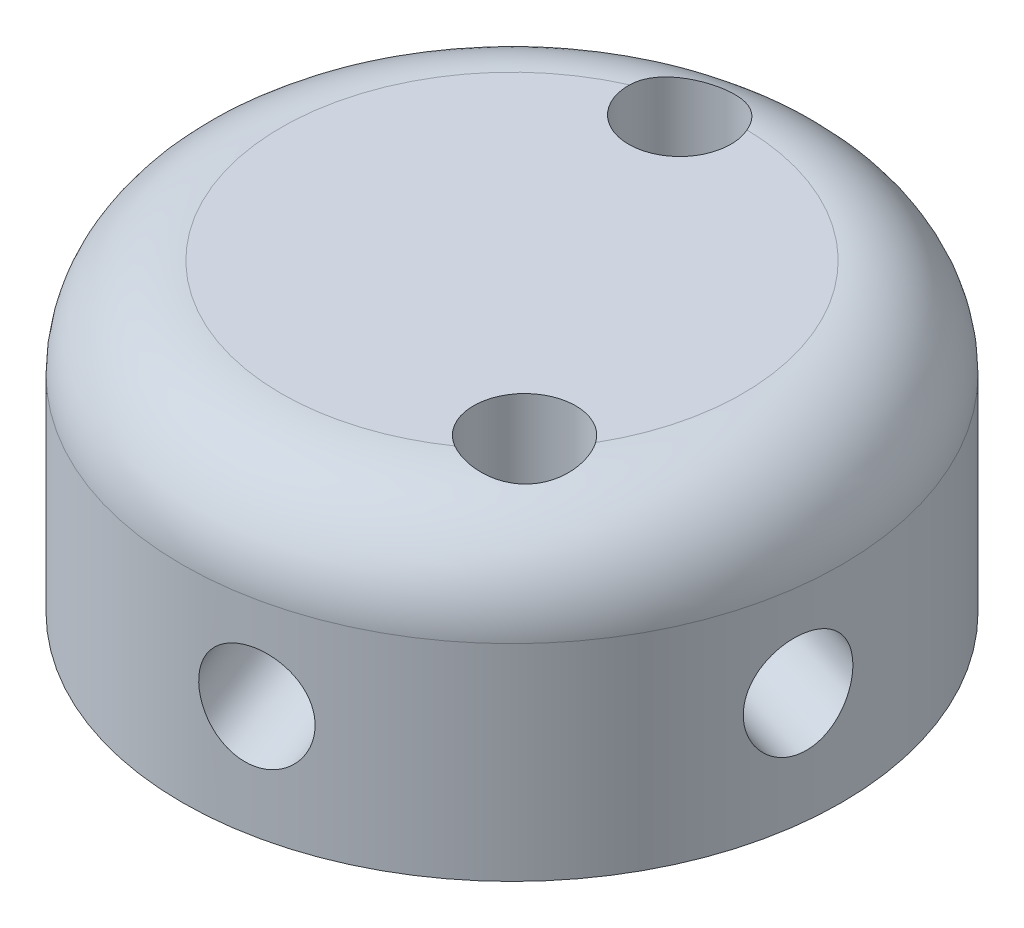
SolidWorks part; units mm, degrees
ref_plane "Front Plane" through (0, 0, 0) normal (0, 0, 1) x (1, 0, 0)
ref_plane "Top Plane" through (0, 0, 0) normal (0, 1, 0) x (1, 0, 0)
ref_plane "Right Plane" through (0, 0, 0) normal (1, 0, 0) x (0, 0, -1)
sketch "Sketch1" plane through (0, 0, 0) normal (0, 1, 0) x (1, 0, 0)
  circle A0 centre (0, 0) radius 10
  dimension "D1" = 20
extrude "Boss-Extrude1" add sketch "Sketch1" along normal blind 3 and the other way blind 10
ref_axis "5hubaxis" through (0, 5.5, 0) along (0, -1, 0)
ref_plane "holeplane" through (-3.3529, -1.0931, 1.8877) normal (0.8382, 0.2733, -0.4719) x (-0.4487, -0.1463, -0.8816)
sketch "Sketch4" plane through (-3.3529, -1.0931, 1.8877) normal (0.8382, 0.2733, -0.4719) x (-0.4487, -0.1463, -0.8816)
  circle A0 centre (0, 0) radius 1.5 construction
  circle A1 centre (0, 0) radius 1.5
extrude "hole" cut sketch "Sketch4" against normal through all
pattern_circular "holecir" count 5 over 360 about axis through (0, 5.5, 0) along (0, -1, 0) of "hole"
sketch "Sketch5" plane through (0, -10, 0) normal (0, -1, 0) x (1, 0, 0)
  line L0 (-10, 0) -> (10, 0) construction
  circle A0 centre (0, 0) radius 10 construction
  text T0 "5"
extrude "Boss-Extrude2" [suppressed] add sketch "Sketch5" along normal blind 1
ref_plane "Plane1" through (0, -5, 0) normal (0, -1, 0) x (-1, 0, 0)
sketch "Sketch6" plane through (0, -5, 0) normal (0, -1, 0) x (-1, 0, 0)
  circle A0 centre (0, 0) radius 3.5
  dimension "D1" = 7
extrude "bearinghole" cut sketch "Sketch6" along normal blind 2.5
sketch "Sketch7" plane through (0, -5, 0) normal (0, -1, 0) x (-1, 0, 0)
  circle A0 centre (0, 0) radius 2
  dimension "D1" = 4
extrude "shafthole" cut sketch "Sketch7" along normal through all
sketch "Sketch8" plane through (0, 3, 0) normal (0, 1, 0) x (1, 0, 0)
  line L0 (-1.9732, 9.8034) -> (0, 0) construction
  line L1 (0, 0) -> (7.3586, -6.7713) construction
  line L2 (0, 0) -> (1.9732, -9.8034) construction
  line L3 (3.4214, -9.3965) -> (2.2297, -3.4761) construction
  line L4 (0, 0) -> (9.9333, -1.1528) construction
  line L5 (9.9939, 0.3502) -> (3.995, 1.0464) construction
  line L6 (0, 0) -> (4.166, 9.0909) construction
  line L7 (2.7552, 9.613) -> (0.2393, 4.1229) construction
  circle A0 centre (0, 0) radius 10 construction
  circle A1 centre (0, 0) radius 6.5 construction
  point P15 (-1.2826, 6.3722)
  point P16 (4.7831, -4.4014)
  dimension "D3" = 13
  dimension "D1" = 36
  dimension "D2" = 36
hole_wizard "Ø3.1 (3.1) Diameter Hole1" positions "Sketch9" profile "Sketch10" hole size "Ø3.1" standard "ISO" end condition through all
sketch "Sketch9" plane through (0, 3, 0) normal (0, 1, 0) x (1, 0, 0)
  point P0 (-1.2826, 6.3722)
  point P3 (4.7831, -4.4014)
sketch "Sketch10" plane through (-1.2826, 3, -6.3722) normal (1, 0, 0) x (0, 0, 1)
  line L0 (0, 0) -> (0, 13)
  line L1 (0, 13) -> (1.55, 13)
  line L2 (1.55, 13) -> (1.55, 0)
  line L5 (1.55, 0) -> (0, 0)
  line L11 (0, -6.35) -> (0, 107.95) construction
  dimension "Thru Hole Dia." = 3.1
  dimension "Thru Hole Depth" = 13
fillet "Fillet2" radius 3 2 edges at (0, 3, 10) (0, -10, 10)
ref_plane "Plane2" through (0, -6.25, 0) normal (0, -1, 0) x (-1, 0, 0)
sketch "Sketch11" plane through (0, -6.25, 0) normal (0, -1, 0) x (-1, 0, 0)
  circle A0 centre (0, 0) radius 10
extrude "Cut-Extrude1" cut sketch "Sketch11" along normal blind 10
